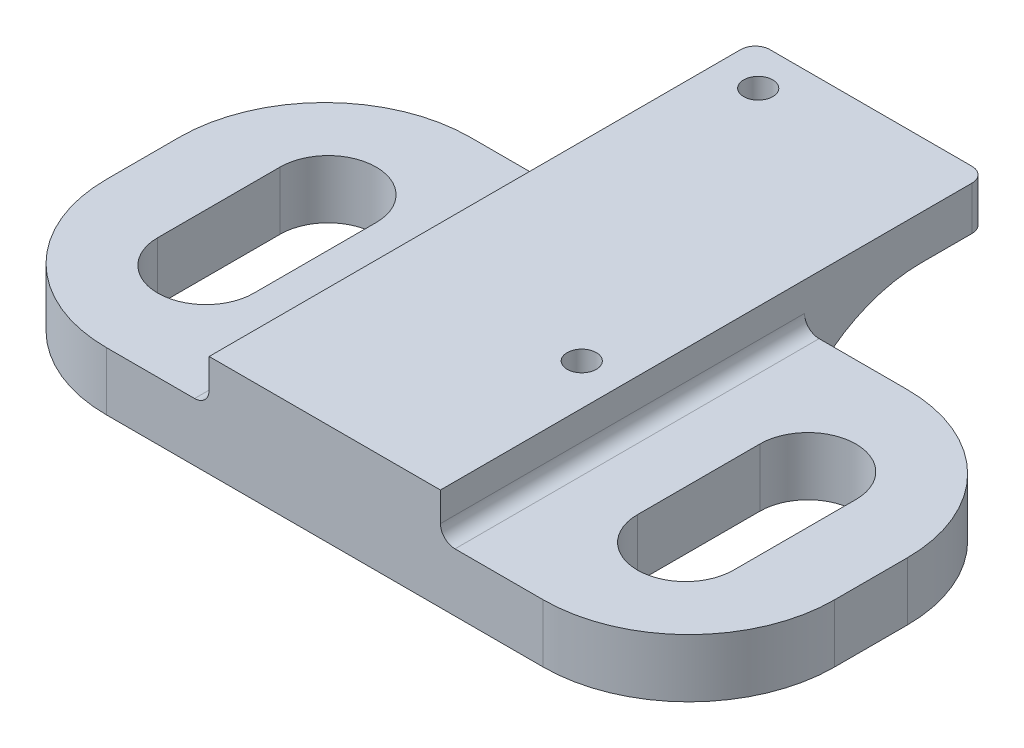
SolidWorks part; units mm, degrees
ref_plane "Front Plane" through (0, 0, 0) normal (0, 0, 1) x (1, 0, 0)
ref_plane "Top Plane" through (0, 0, 0) normal (0, 1, 0) x (1, 0, 0)
ref_plane "Right Plane" through (0, 0, 0) normal (1, 0, 0) x (0, 0, -1)
sketch "Sketch1" plane through (0, 0, 0) normal (0, 1, 0) x (1, 0, 0)
  line L1 (0, 0) -> (50, 0)
  line L2 (0, 0) -> (0, 25)
  line L3 (0, 25) -> (50, 25)
  line L4 (50, 0) -> (50, 25)
  dimension "D1" = 50
  dimension "D2" = 25
extrude "Boss-Extrude1" add sketch "Sketch1" along normal blind 4
sketch "Sketch2" plane through (0, 4, 0) normal (0, 1, 0) x (1, 0, 0)
  line L1 (17.06, 37.5) -> (32.94, 37.5)
  line L2 (17.06, 37.5) -> (17.06, 0)
  line L3 (17.06, 0) -> (32.94, 0)
  line L4 (32.94, 37.5) -> (32.94, 0)
  line L5 (0, 0) -> (50, 0) construction
  point P10 (25, 0)
  point P11 (25, 0)
  dimension "D1" = 15.88
  dimension "D2" = 37.5
extrude "Boss-Extrude2" add sketch "Sketch2" along normal blind 3
hole_wizard "M6 Clearance Slot1" positions "Sketch3" profile "Sketch4" size "M6" standard "ANSI Metric" slot yes end condition up to next
sketch "Sketch3" plane through (0, 4, 0) normal (0, 1, 0) x (1, 0, 0)
  line L0 (0, 25) -> (0, 0) construction
  line L1 (17.06, 25) -> (0, 25) construction
  line L2 (50, 25) -> (32.94, 25) construction
  line L3 (8.53, 5) -> (8.53, 20) construction
  point P0 (8.53, 12.5)
  point P2 (41.47, 12.5)
  point P9 (0, 12.5)
  point P13 (8.53, 25)
  point P17 (41.47, 25)
  dimension "D1" = 15
sketch "Sketch4" plane through (8.53, 4, -12.5) normal (1, 0, 0) x (0, 0, 1)
  line L0 (0, 0) -> (0, 4)
  line L1 (0, 4) -> (3.3, 4)
  line L2 (3.3, 4) -> (3.3, 0)
  line L5 (3.3, 0) -> (0, 0)
  line L11 (0, -6.35) -> (0, 107.95) construction
  dimension "Thru Hole Dia." = 6.6
  dimension "Thru Hole Depth" = 4
hole_wizard "M3 Clearance Hole1" positions "Sketch5" profile "Sketch6" hole size "M3" standard "ANSI Metric" end condition through all
sketch "Sketch5" plane through (0, 7, 0) normal (0, 1, 0) x (1, 0, 0)
  point P0 (19.96, 34.8)
  point P3 (30.12, 12.525)
sketch "Sketch6" plane through (19.96, 7, -34.8) normal (1, 0, 0) x (0, 0, 1)
  line L0 (0, 0) -> (0, 7)
  line L1 (0, 7) -> (1, 7)
  line L2 (1, 7) -> (1, 0)
  line L5 (1, 0) -> (0, 0)
  line L11 (0, -6.35) -> (0, 107.95) construction
  dimension "Thru Hole Dia." = 2
  dimension "Thru Hole Depth" = 7
fillet "Fillet3" radius 10 4 edges at (50, 2, -25) (50, 2, 0) (0, 2, 0) (0, 2, -25)
fillet "Fillet4" radius 10 1 edges at (25, 4, -25)
fillet "Fillet5" radius 1 4 edges at (32.94, 4, -12.5) (17.06, 4, -12.5) (32.94, 5.5, -37.5) (17.06, 5.5, -37.5)
